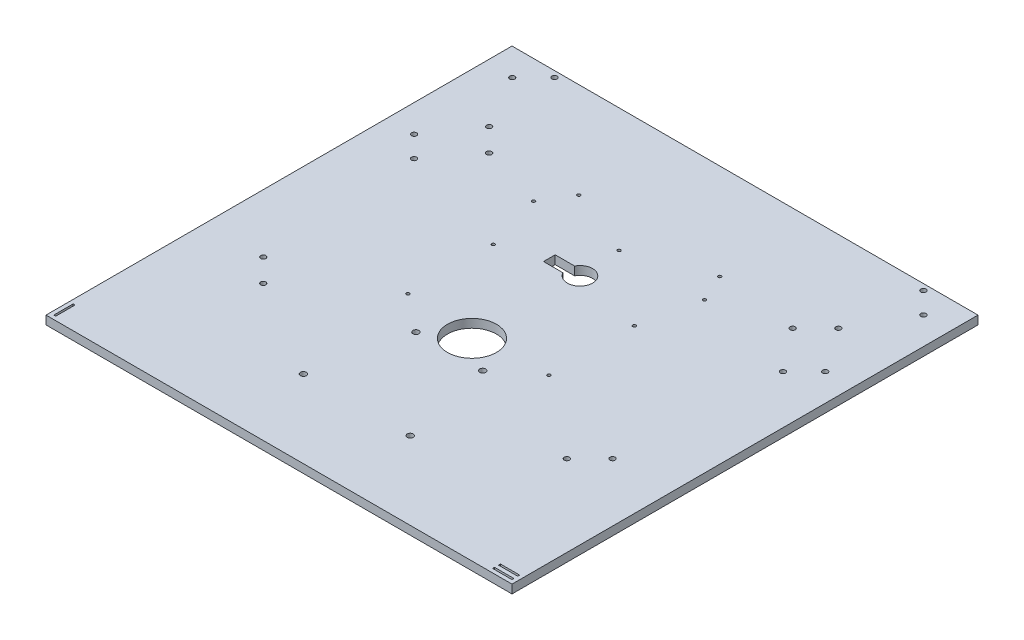
SolidWorks part; units mm, degrees
material "Acrylic (Medium-high impact)"
ref_plane "Front Plane" through (0, 0, 0) normal (0, 0, 1) x (1, 0, 0)
ref_plane "Top Plane" through (0, 0, 0) normal (0, 1, 0) x (1, 0, 0)
ref_plane "Right Plane" through (0, 0, 0) normal (1, 0, 0) x (0, 0, -1)
sketch "Sketch2" plane through (0, 0, 0) normal (0, 1, 0) x (1, 0, 0)
  line L1 (0, 0) -> (304.8, 0)
  line L2 (0, 0) -> (0, 304.8)
  line L3 (0, 304.8) -> (304.8, 304.8)
  line L4 (304.8, 0) -> (304.8, 304.8)
  dimension "D1" = 304.8
  dimension "D2" = 304.8
extrude "Boss-Extrude1" add sketch "Sketch2" along normal blind 5.588
sketch "Sketch4" plane through (0, 5.588, 0) normal (0, 1, 0) x (1, 0, 0)
  line L0 (0, 304.8) -> (0, 0) construction
  line L1 (2.54, 2.54) -> (3.81, 2.54)
  line L2 (2.54, 2.54) -> (2.54, 15.24)
  line L3 (2.54, 15.24) -> (3.81, 15.24)
  line L4 (3.81, 2.54) -> (3.81, 15.24)
  line L5 (2.54, 302.26) -> (3.81, 302.26) construction
  line L6 (2.54, 302.26) -> (2.54, 289.56) construction
  line L7 (2.54, 289.56) -> (3.81, 289.56) construction
  line L8 (3.81, 302.26) -> (3.81, 289.56) construction
  line L9 (6.35, 302.26) -> (7.62, 302.26) construction
  line L10 (6.35, 302.26) -> (6.35, 289.56) construction
  line L11 (6.35, 289.56) -> (7.62, 289.56) construction
  line L12 (7.62, 302.26) -> (7.62, 289.56) construction
  line L13 (304.8, 304.8) -> (0, 304.8) construction
  line L14 (0, 0) -> (304.8, 0) construction
  line L15 (304.8, 0) -> (304.8, 304.8) construction
  line L16 (302.26, 2.54) -> (289.56, 2.54)
  line L17 (302.26, 2.54) -> (302.26, 3.81)
  line L18 (302.26, 3.81) -> (289.56, 3.81)
  line L19 (289.56, 2.54) -> (289.56, 3.81)
  line L20 (302.26, 6.35) -> (289.56, 6.35)
  line L21 (302.26, 6.35) -> (302.26, 7.62)
  line L22 (302.26, 7.62) -> (289.56, 7.62)
  line L23 (289.56, 6.35) -> (289.56, 7.62)
  dimension "D1" = 12.7
  dimension "D2" = 1.27
  dimension "D3" = 2.54
  dimension "D4" = 2.54
  dimension "D5" = 2.54
  dimension "D6" = 2.54
  dimension "D7" = 2.54
  dimension "D8" = 2.54
  dimension "D9" = 2.54
  dimension "D10" = 2.54
extrude "Cut-Extrude1" cut sketch "Sketch4" against normal through all
sketch "Sketch5" plane through (0, 5.588, 0) normal (0, 1, 0) x (1, 0, 0)
  line L0 (0, 304.8) -> (0, 0) construction
  line L1 (34.5465, 268.1122) -> (263.4005, 268.1122)
  line L2 (34.5465, 268.1122) -> (34.5465, 281.0662)
  line L3 (34.5465, 281.0662) -> (263.4005, 281.0662)
  line L4 (263.4005, 268.1122) -> (263.4005, 281.0662)
  line L5 (304.8, 0) -> (304.8, 304.8) construction
  line L6 (304.8, 304.8) -> (0, 304.8) construction
  dimension "D1" = 34.5465
  dimension "D2" = 41.3995
  dimension "D3" = 23.7338
  dimension "D4" = 12.954
extrude "Cut-Extrude2" cut sketch "Sketch5" against normal blind 0.254
sketch "Sketch6" plane through (0, 5.588, 0) normal (0, 1, 0) x (1, 0, 0)
  circle A0 centre (152.48, 126.1263) radius 15.748 construction
  circle A1 centre (152.48, 126.1263) radius 15.748 construction
  circle A2 centre (152.48, 126.1263) radius 16.002
  circle A3 centre (31.75, 300.8321) radius 1.7 construction
  circle A4 centre (17.9387, 287.0209) radius 1.7 construction
  circle A5 centre (273.05, 300.8321) radius 1.7 construction
  circle A6 centre (286.8612, 287.0209) radius 1.7 construction
  circle A7 centre (286.8612, 222.7817) radius 1.7 construction
  circle A8 centre (273.05, 208.9705) radius 1.7 construction
  circle A9 centre (31.75, 208.9705) radius 1.7 construction
  circle A10 centre (17.9388, 222.7817) radius 1.7 construction
  circle A11 centre (31.75, 300.8321) radius 1.7
  circle A12 centre (17.9387, 287.0209) radius 1.7
  circle A13 centre (273.05, 300.8321) radius 1.7
  circle A14 centre (286.8612, 287.0209) radius 1.7
  circle A15 centre (286.8612, 222.7817) radius 1.7
  circle A16 centre (273.05, 208.9705) radius 1.7
  circle A17 centre (31.75, 208.9705) radius 1.7
  circle A18 centre (17.9388, 222.7817) radius 1.7
  circle A19 centre (38.1788, 103.933) radius 1.7 construction
  circle A20 centre (53.133, 88.9788) radius 1.7 construction
  circle A21 centre (251.667, 88.9788) radius 1.7 construction
  circle A22 centre (266.6212, 103.933) radius 1.7 construction
  circle A23 centre (266.6212, 251.667) radius 1.7 construction
  circle A24 centre (251.667, 236.7127) radius 1.7 construction
  circle A25 centre (53.133, 236.7127) radius 1.7 construction
  circle A26 centre (38.1788, 251.667) radius 1.7 construction
  circle A27 centre (38.1788, 103.933) radius 1.7
  circle A28 centre (53.133, 88.9788) radius 1.7
  circle A29 centre (251.667, 88.9788) radius 1.7
  circle A30 centre (266.6212, 103.933) radius 1.7
  circle A31 centre (266.6212, 251.667) radius 1.7
  circle A32 centre (251.667, 236.7127) radius 1.7
  circle A33 centre (53.133, 236.7127) radius 1.7
  circle A34 centre (38.1788, 251.667) radius 1.7
  circle A35 centre (117.555, 50.8216) radius 4.5 construction
  circle A36 centre (187.405, 50.8216) radius 4.5 construction
  circle A37 centre (174.3081, 111.328) radius 4.5 construction
  circle A38 centre (130.6519, 111.328) radius 4.5 construction
  circle A39 centre (117.555, 50.8216) radius 4.5 construction
  circle A40 centre (187.405, 50.8216) radius 4.5 construction
  circle A41 centre (174.3081, 111.328) radius 4.5 construction
  circle A42 centre (130.6519, 111.328) radius 4.5 construction
  circle A43 centre (130.6519, 111.328) radius 1.96
  circle A44 centre (174.3081, 111.328) radius 1.96
  circle A45 centre (187.405, 50.8216) radius 1.96
  circle A46 centre (117.555, 50.8216) radius 1.96
  dimension "D1" = 0.254
  dimension "D2" = 2.54
extrude "Cut-Extrude3" cut sketch "Sketch6" against normal through all
sketch "Sketch7" plane through (0, 5.588, 0) normal (0, 1, 0) x (1, 0, 0)
  line L0 (152.4, 304.8) -> (152.4, 0) construction
  line L1 (304.8, 304.8) -> (0, 304.8) construction
  line L2 (0, 0) -> (304.8, 0) construction
  line L4 (145.0768, 200.66) -> (132.3768, 200.66)
  line L5 (145.0768, 200.66) -> (145.0768, 193.04) construction
  line L6 (145.0768, 193.04) -> (132.3768, 193.04)
  line L7 (132.3768, 200.66) -> (132.3768, 193.04)
  circle A0 centre (152.4, 196.85) radius 8.255 construction
  arc A1 (145.0768, 200.66) -> (145.0768, 193.04) centre (152.4, 196.85) cw
  dimension "D2" = 16.51
  dimension "D1" = 107.95
  dimension "D3" = 7.62
  dimension "D4" = 12.7
extrude "Cut-Extrude4" cut sketch "Sketch7" against normal through all
sketch "Sketch8" plane through (0, 5.588, 0) normal (0, 1, 0) x (1, 0, 0)
  circle A0 centre (94.94, 223.995) radius 0.762 construction
  circle A1 centre (150.82, 223.995) radius 0.762 construction
  circle A2 centre (206.7, 223.995) radius 0.762 construction
  circle A3 centre (94.94, 223.995) radius 0.762 construction
  circle A4 centre (150.82, 223.995) radius 0.762 construction
  circle A5 centre (206.7, 223.995) radius 0.762 construction
  circle A6 centre (206.7, 223.995) radius 1.016
  circle A7 centre (150.82, 223.995) radius 1.016
  circle A8 centre (94.94, 223.995) radius 1.016
  dimension "D1" = 0.254
extrude "Cut-Extrude5" cut sketch "Sketch8" against normal through all
sketch "Sketch9" plane through (0, 5.588, 0) normal (0, 1, 0) x (1, 0, 0)
  circle A0 centre (106.3, 242.18) radius 0.762 construction
  circle A1 centre (106.3, 186.3) radius 0.762 construction
  circle A2 centre (106.3, 130.42) radius 0.762 construction
  circle A3 centre (198.5, 130.42) radius 0.762 construction
  circle A4 centre (198.5, 186.3) radius 0.762 construction
  circle A5 centre (198.5, 242.18) radius 0.762 construction
  circle A6 centre (106.3, 242.18) radius 0.762 construction
  circle A7 centre (106.3, 186.3) radius 0.762 construction
  circle A8 centre (106.3, 130.42) radius 0.762 construction
  circle A9 centre (198.5, 130.42) radius 0.762 construction
  circle A10 centre (198.5, 186.3) radius 0.762 construction
  circle A11 centre (198.5, 242.18) radius 0.762 construction
  circle A12 centre (106.3, 242.18) radius 1.016
  circle A13 centre (106.3, 186.3) radius 1.016
  circle A14 centre (106.3, 130.42) radius 1.016
  circle A15 centre (198.5, 130.42) radius 1.016
  circle A16 centre (198.5, 186.3) radius 1.016
  circle A17 centre (198.5, 242.18) radius 1.016
  dimension "D1" = 0.254
extrude "Cut-Extrude6" cut sketch "Sketch9" against normal through all
sketch "Sketch10" plane through (0, 5.588, 0) normal (0, 1, 0) x (1, 0, 0)
  line L1 (30.0638, 287.1688) -> (266.0755, 287.1688)
  line L2 (30.0638, 287.1688) -> (30.0638, 264.2232)
  line L3 (30.0638, 264.2232) -> (266.0755, 264.2232)
  line L4 (266.0755, 287.1688) -> (266.0755, 264.2232)
extrude "Boss-Extrude3" add sketch "Sketch10" against normal through all
equation "\"D8@Sketch4\"=\"D6@Sketch4\""
